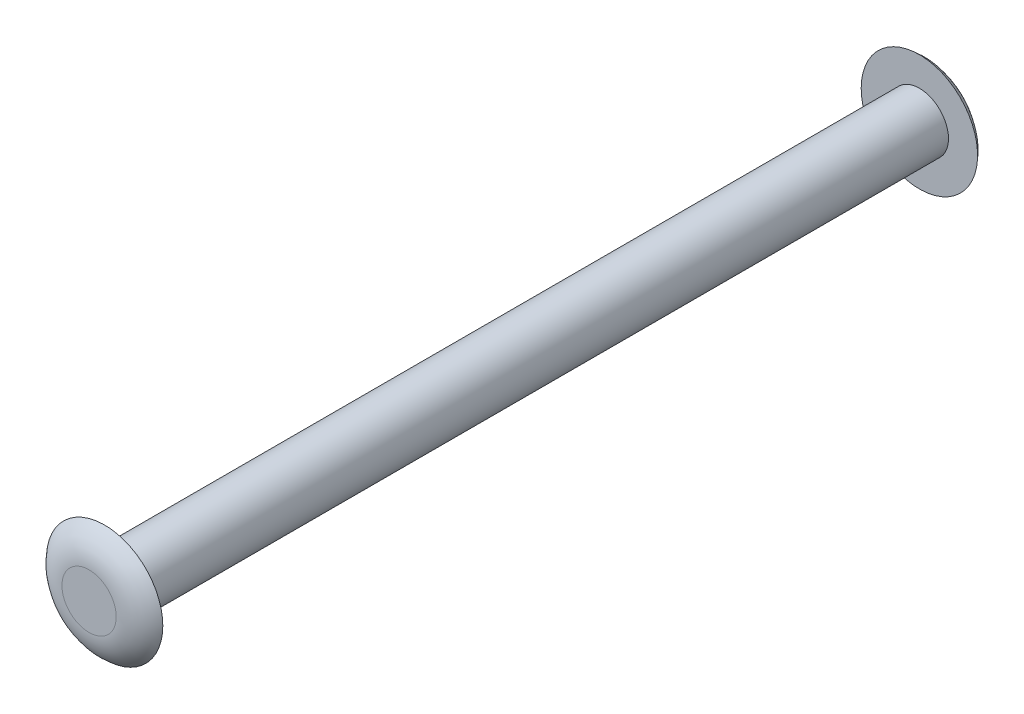
SolidWorks part; units mm, degrees
ref_plane "Front Plane" through (0, 0, 0) normal (0, 0, 1) x (1, 0, 0)
ref_plane "Top Plane" through (0, 0, 0) normal (0, 1, 0) x (1, 0, 0)
ref_plane "Right Plane" through (0, 0, 0) normal (1, 0, 0) x (0, 0, -1)
sketch "Sketch1" plane through (0, 0, 0) normal (0, 0, 1) x (1, 0, 0)
  circle A0 centre (0, 0) radius 3.75
  dimension "D1" = 7.5
extrude "Boss-Extrude1" add sketch "Sketch1" along normal blind 105
ref_plane "Plane1" through (-3.75, 0, 0) normal (-1, 0, 0) x (0, 0, 1)
sketch "Sketch2" plane through (-3.75, 0, 0) normal (-1, 0, 0) x (0, 0, 1)
  circle A0 centre (20.5, 0) radius 1
  point P2 (0, 0)
  dimension "D2" = 2
  dimension "D1" = 20.5
extrude "Cut-Extrude1" [suppressed] cut sketch "Sketch2" against normal through all contours A0
pattern_linear "LPattern2" [suppressed] count 3 spacing 22.5 of bodies 102
sketch "Sketch3" plane through (0, 0, 105) normal (0, 0, 1) x (1, 0, 0)
  circle A0 centre (0, 0) radius 7.5
  dimension "D1" = 15
extrude "Boss-Extrude2" add sketch "Sketch3" along normal blind 2
sketch "Sketch4" plane through (0, 0, 0) normal (0, 0, -1) x (-1, 0, 0)
  circle A0 centre (0, 0) radius 7.5
  dimension "D1" = 15
extrude "Boss-Extrude3" add sketch "Sketch4" along normal blind 2
fillet "Fillet1" radius 5 2 edges at (7.5, 0, 107) (-7.5, 0, -2)
